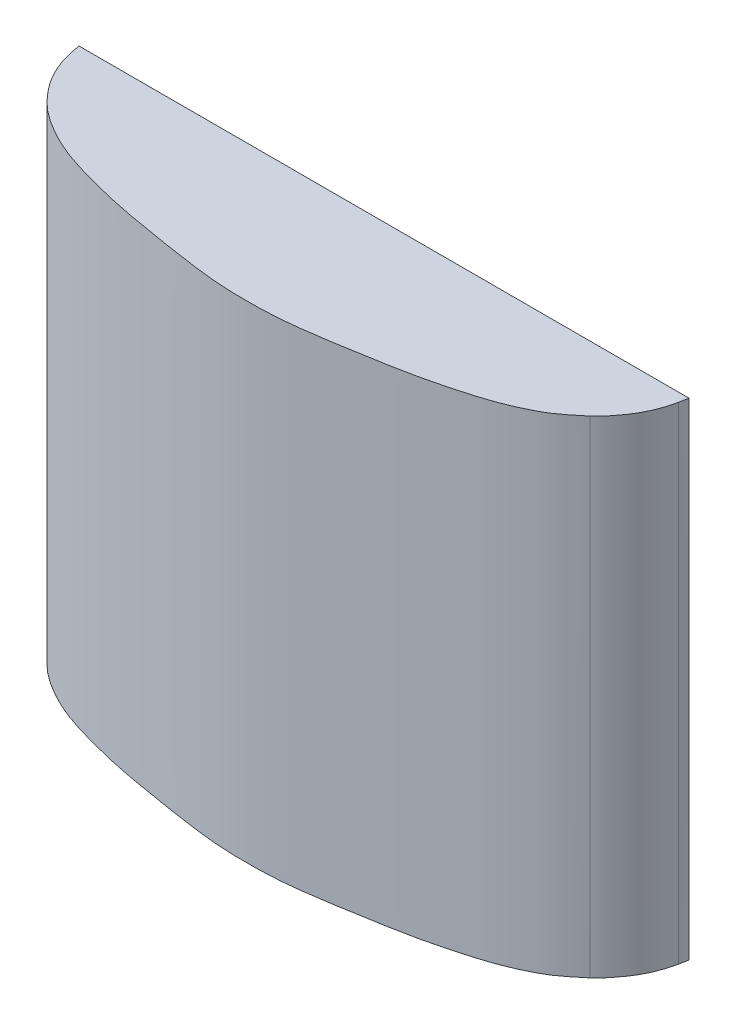
SolidWorks part; units mm, degrees
ref_plane "Front Plane" through (0, 0, 0) normal (0, 0, 1) x (1, 0, 0)
ref_plane "Top Plane" through (0, 0, 0) normal (0, 1, 0) x (1, 0, 0)
ref_plane "Right Plane" through (0, 0, 0) normal (1, 0, 0) x (0, 0, -1)
sketch "Sketch2" plane through (-0.0001, -112.6002, -0.0009) normal (0, -1, 0) x (1, 0, 0)
  line L13 (178.231, -11.965) -> (182.4206, -11.965)
  line L14 (182.4206, -11.965) -> (197.9206, -11.965)
  line L16 (182.4206, -11.965) -> (197.9206, -11.965)
  line L18 (199.5206, -11.965) -> (215.0206, -11.965)
  line L20 (197.9206, -11.965) -> (199.5206, -11.965)
  line L21 (197.9206, -11.965) -> (199.5206, -11.965)
  line L22 (199.5206, -11.965) -> (215.0206, -11.965)
  line L23 (266.323, -11.965) -> (270.7576, -11.965)
  line L24 (178.231, -11.965) -> (182.4206, -11.965)
  line L34 (266.323, -11.965) -> (270.7576, -11.965)
  line L102 (216.6206, -11.965) -> (232.1206, -11.965)
  line L104 (216.6206, -11.965) -> (232.1206, -11.965)
  line L106 (215.0206, -11.965) -> (216.6206, -11.965)
  line L107 (215.0206, -11.965) -> (216.6206, -11.965)
  line L108 (233.7206, -11.965) -> (249.2206, -11.965)
  line L113 (233.7206, -11.965) -> (249.2206, -11.965)
  line L117 (250.8206, -11.965) -> (266.323, -11.965)
  line L119 (232.1206, -11.965) -> (233.7206, -11.965)
  line L120 (232.1206, -11.965) -> (233.7206, -11.965)
  line L121 (250.8206, -11.965) -> (266.323, -11.965)
  line L127 (249.2206, -11.965) -> (250.8206, -11.965)
  line L128 (249.2206, -11.965) -> (250.8206, -11.965)
  spline S6 degree 3 poles (-1720.3265, -197.3659) (2277.4424, 97.9175) (-1736.4443, -119.2476) (2261.4301, 176.0426) knots -1.603146 -1.603146 -1.603146 -1.603146 3.59757 3.59757 3.59757 3.59757 only from (270.7576, -11.965) to (270.4993, -10.6014)
  spline S7 degree 3 poles (2259.5444, 107.4758) (-354.6377, -294.3138) (295.0415, -88.9532) (269.9529, -8.5848) (269.769, -8.0864) (269.3518, -7.1235) (269.1177, -6.6573) (268.5974, -5.7564) (268.3125, -5.3208) (267.7102, -4.4693) (267.3957, -4.0515) (266.7294, -3.2384) (266.3797, -2.8492) (248.7358, 14.289) (184.8722, -24.6713) (1492.1945, 1576.7037) knots -2.477843 -2.477843 -2.477843 -2.477843 0.015625 0.015625 0.03125 0.03125 0.046875 0.046875 0.0625 0.0625 0.078125 0.078125 0.09375 0.09375 0.819188 0.819188 0.819188 0.819188 only from (270.4993, -10.6014) to (265.5929, -2.1021)
  spline S8 degree 3 poles (-964.0462, -1578.9308) (285.771, -48.0003) (282.6406, -15.9581) (264.6404, -1.3011) (264.438, -1.1401) (264.0328, -0.8184) (263.8303, -0.6574) (263.2186, -0.1797) (262.8051, 0.1321) (261.9411, 0.7113) (261.4867, 0.9765) (260.5735, 1.4651) (260.1121, 1.692) (259.1857, 2.1331) (258.72, 2.3449) (257.313, 2.9444) (256.3601, 3.2911) (254.4354, 3.9165) (253.4641, 4.197) (251.5159, 4.7383) (250.5385, 4.9972) (248.5757, 5.4865) (247.5893, 5.7129) (245.6055, 6.1271) (244.6085, 6.3157) (242.6108, 6.68) (241.6104, 6.8569) (238.6063, 7.376) (236.5979, 7.7075) (233.5806, 8.1473) (232.574, 8.2858) (230.5568, 8.5261) (229.5462, 8.6275) (227.5172, 8.7577) (226.499, 8.7898) (224.4598, 8.8194) (223.4416, 8.8158) (221.4089, 8.7611) (220.3946, 8.7061) (218.3708, 8.5354) (217.3613, 8.4184) (214.3359, 8.0286) (212.3217, 7.7231) (209.3082, 7.2339) (208.3046, 7.066) (206.2989, 6.722) (205.2967, 6.5463) (203.2963, 6.1738) (202.298, 5.9768) (200.3095, 5.5399) (199.3181, 5.301) (197.3455, 4.7932) (196.3633, 4.5282) (194.4106, 3.9663) (193.4406, 3.6682) (191.5299, 2.9926) (190.5898, 2.6137) (188.7482, 1.7509) (187.8444, 1.269) (186.0801, 0.2061) (185.2337, -0.37) (184.0471, -1.3378) (183.666, -1.6785) (161.4264, -23.6127) (187.8547, -117.0108) (668.511, 1936.6248) knots -0.683502 -0.683502 -0.683502 -0.683502 0.009929 0.009929 0.017741 0.017741 0.025554 0.025554 0.041179 0.041179 0.056804 0.056804 0.072429 0.072429 0.088054 0.088054 0.119304 0.119304 0.150554 0.150554 0.181804 0.181804 0.213054 0.213054 0.244304 0.244304 0.275554 0.275554 0.338054 0.338054 0.369304 0.369304 0.400554 0.400554 0.431804 0.431804 0.463054 0.463054 0.494304 0.494304 0.525554 0.525554 0.588054 0.588054 0.619304 0.619304 0.650554 0.650554 0.681804 0.681804 0.713054 0.713054 0.744304 0.744304 0.775554 0.775554 0.806804 0.806804 0.838054 0.838054 0.869304 0.869304 0.884929 0.884929 1.820444 1.820444 1.820444 1.820444 only from (265.5929, -2.1021) to (182.2469, -3.1696)
  spline S9 degree 3 poles (-1660.2872, 774.0819) (2092.4652, -742.3478) (-1693.0443, 801.3189) (1937.5579, -957.7355) knots -32.313277 -32.313277 -32.313277 -32.313277 30.347883 30.347883 30.347883 30.347883 only from (182.2469, -3.1696) to (180.847, -4.9772)
  spline S10 degree 3 poles (-1660.7809, 774.2814) (2092.7924, -742.4813) (-1693.194, 801.3922) (1937.5441, -957.7288) knots -32.316025 -32.316025 -32.316025 -32.316025 30.347804 30.347804 30.347804 30.347804 only from (180.847, -4.9772) to (180.2784, -5.8735)
  spline S11 degree 3 poles (509.1095, 445.9436) (3280.8168, -1548.075) (251.36, 167.6916) (179.1959, -8.1203) (179.0707, -8.4587) (178.8445, -9.1368) (178.7429, -9.478) (178.471, -10.5073) (178.3332, -11.2013) (173.4299, -47.8054) (288.3915, -105.226) (-1805.3979, 234.1853) knots -32.852714 -32.852714 -32.852714 -32.852714 0.125 0.125 0.1875 0.1875 0.25 0.25 0.375 0.375 6.768835 6.768835 6.768835 6.768835 only from (180.2784, -5.8735) to (178.231, -11.965)
  spline S12 degree 3 poles (270.7576, -11.965) (270.6871, -11.5094) (270.5926, -11.0554) (270.4993, -10.6014) knots 0.939542 0.939542 0.939542 0.939542 1 1 1 1
  spline S13 degree 3 poles (270.4993, -10.6014) (270.3951, -10.0912) (270.2653, -9.5858) (269.9529, -8.5848) (269.769, -8.0864) (269.3518, -7.1235) (269.1177, -6.6573) (268.5974, -5.7564) (268.3125, -5.3208) (267.7102, -4.4693) (267.3957, -4.0515) (266.7294, -3.2384) (266.3797, -2.8492) (265.872, -2.3561) (265.7335, -2.2278) (265.5929, -2.1021) knots 0 0 0 0 0.015625 0.015625 0.03125 0.03125 0.046875 0.046875 0.0625 0.0625 0.078125 0.078125 0.09375 0.09375 0.099446 0.099446 0.099446 0.099446
  spline S14 degree 3 poles (265.5929, -2.1021) (265.3476, -1.8831) (265.0958, -1.6719) (264.6404, -1.3011) (264.438, -1.1401) (264.0328, -0.8184) (263.8303, -0.6574) (263.2186, -0.1797) (262.8051, 0.1321) (261.9411, 0.7113) (261.4867, 0.9765) (260.5735, 1.4651) (260.1121, 1.692) (259.1857, 2.1331) (258.72, 2.3449) (257.313, 2.9444) (256.3601, 3.2911) (254.4354, 3.9165) (253.4641, 4.197) (251.5159, 4.7383) (250.5385, 4.9972) (248.5757, 5.4865) (247.5893, 5.7129) (245.6055, 6.1271) (244.6085, 6.3157) (242.6108, 6.68) (241.6104, 6.8569) (238.6063, 7.376) (236.5979, 7.7075) (233.5806, 8.1473) (232.574, 8.2858) (230.5568, 8.5261) (229.5462, 8.6275) (227.5172, 8.7577) (226.499, 8.7898) (224.4598, 8.8194) (223.4416, 8.8158) (221.4089, 8.7611) (220.3946, 8.7061) (218.3708, 8.5354) (217.3613, 8.4184) (214.3359, 8.0286) (212.3217, 7.7231) (209.3082, 7.2339) (208.3046, 7.066) (206.2989, 6.722) (205.2967, 6.5463) (203.2963, 6.1738) (202.298, 5.9768) (200.3095, 5.5399) (199.3181, 5.301) (197.3455, 4.7932) (196.3633, 4.5282) (194.4106, 3.9663) (193.4406, 3.6682) (191.5299, 2.9926) (190.5898, 2.6137) (188.7482, 1.7509) (187.8444, 1.269) (186.0801, 0.2061) (185.2337, -0.37) (184.0471, -1.3378) (183.666, -1.6785) (182.9353, -2.3992) (182.5835, -2.7795) (182.2469, -3.1696) knots 0 0 0 0 0.009929 0.009929 0.017741 0.017741 0.025554 0.025554 0.041179 0.041179 0.056804 0.056804 0.072429 0.072429 0.088054 0.088054 0.119304 0.119304 0.150554 0.150554 0.181804 0.181804 0.213054 0.213054 0.244304 0.244304 0.275554 0.275554 0.338054 0.338054 0.369304 0.369304 0.400554 0.400554 0.431804 0.431804 0.463054 0.463054 0.494304 0.494304 0.525554 0.525554 0.588054 0.588054 0.619304 0.619304 0.650554 0.650554 0.681804 0.681804 0.713054 0.713054 0.744304 0.744304 0.775554 0.775554 0.806804 0.806804 0.838054 0.838054 0.869304 0.869304 0.884929 0.884929 0.900554 0.900554 0.900554 0.900554
  spline S15 degree 3 poles (182.2469, -3.1696) (181.753, -3.7429) (181.2798, -4.3426) (180.847, -4.9772) knots 0 0 0 0 0.685452 0.685452 0.685452 0.685452
  spline S16 degree 3 poles (180.847, -4.9772) (180.6483, -5.2683) (180.4582, -5.5669) (180.2784, -5.8735) knots 0.685452 0.685452 0.685452 0.685452 1 1 1 1
  spline S17 degree 3 poles (180.2784, -5.8735) (179.9209, -6.4846) (179.6054, -7.1226) (179.1959, -8.1203) (179.0707, -8.4587) (178.8445, -9.1368) (178.7429, -9.478) (178.471, -10.5073) (178.3332, -11.2013) (178.2364, -11.9238) (178.2337, -11.9444) (178.231, -11.965) knots 0 0 0 0 0.125 0.125 0.1875 0.1875 0.25 0.25 0.375 0.375 0.378667 0.378667 0.378667 0.378667
  dimension "D1" = 0
extrude "Boss-Extrude1" add sketch "Sketch2" along normal up to surface (73.81 mm away)
equation "\"tubewidth\"= 3"
